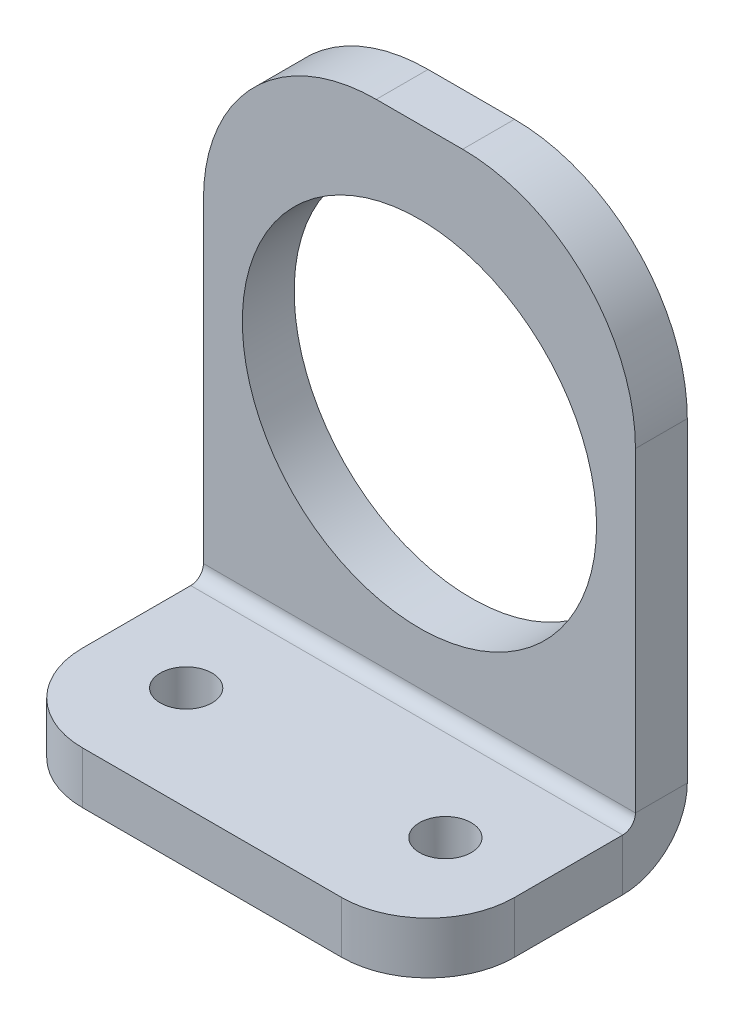
SolidWorks part; units mm, degrees
note: The reader was unsure of these and kept them because the rebuilt part matched: thickness of "基体-法兰1", "边线-法兰1", "钣金1", "钣金2", "钣金3", "钣金4"; flange length of "边线-法兰1".
ref_plane "前视基准面" through (0, 0, 0) normal (0, 0, 1) x (1, 0, 0)
ref_plane "上视基准面" through (0, 0, 0) normal (0, 1, 0) x (1, 0, 0)
ref_plane "右视基准面" through (0, 0, 0) normal (1, 0, 0) x (0, 0, -1)
sketch "草图1" plane through (0, 0, 0) normal (0, 0, 1) x (1, 0, 0)
  line L1 (12.5, -16) -> (-12.5, -16)
  line L2 (12.5, -16) -> (12.5, 16)
  line L3 (12.5, 16) -> (-12.5, 16)
  line L4 (-12.5, -16) -> (-12.5, 16)
  line L5 (12.5, -16) -> (-12.5, 16) construction
  line L6 (12.5, 16) -> (-12.5, -16) construction
  point P0 (0, 0)
  dimension "D1" = 25
  dimension "D2" = 32
base flange "基体-法兰1" sketch "草图1" thickness 3 reverse thickness direction no parameters "D1"=0.7366
edge flange "边线-法兰1" sketch "草图12" flange angle 90 flange length 15 flange position material inside bend radius 0.7366 thickness 3 relief rectangular parameters "D6"=10
sketch "草图12" plane through (0, -16, 0) normal (0, -1, 0) x (1, 0, 0)
  line L0 (-12.5, 0) -> (12.5, 0) construction
  line L1 (-12.5, 0) -> (12.5, 0)
  line L2 (-12.5, 0) -> (-12.5, 12)
  line L3 (-12.5, 12) -> (12.5, 12)
  line L4 (12.5, 12) -> (12.5, 0)
bend "边线折弯1" bend radius 0.7366 bend angle 90 parameters "D5"=1
sketch "草图13" plane through (0, 0, 0) normal (0, 0, 1) x (1, 0, 0)
  line L0 (12.5, -16) -> (-12.5, -16) construction
  line L3 (-12.5, 16) -> (-12.5, -12.2634) construction
  circle A0 centre (0, 1) radius 10.25
  dimension "D1" = 20.5
  dimension "D2" = 17
  dimension "D3" = 12.5
extrude "切除-拉伸1" cut sketch "草图13" against normal blind 10 normal cut yes
sketch "草图15" plane through (0, -13, 0) normal (0, 1, 0) x (1, 0, 0)
  line L0 (0, -0.7366) -> (0, -12) construction
  line L3 (-12.5, -0.7366) -> (12.5, -0.7366) construction
  line L5 (12.5, -12) -> (-12.5, -12) construction
  circle A0 centre (-7.5, -6) radius 1.5
  circle A1 centre (7.5, -6) radius 1.5
  dimension "D1" = 3
  dimension "D2" = 15
  dimension "D3" = 6
extrude "切除-拉伸2" cut sketch "草图15" against normal blind 10 normal cut yes
fillet "圆角1" radius 10 2 edges at (12.5, 16, -1.5) (-12.5, 16, -1.5)
fillet "圆角2" radius 5 2 edges at (12.5, -14.5, 12) (-12.5, -14.5, 12)
sketch "折弯-线1" [suppressed] plane through (0, 0, 0) normal (0, 1, 0) x (1, 0, 0)
sketch "边界框1" [suppressed] plane through (0, 0, 0) normal (0, 1, 0) x (1, 0, 0)
sheet metal parameters "钣金1" thickness 3 parameters "D1"=0.7366
flat pattern "平板型式1" [suppressed]
sketch "折弯-线2" plane through (0, 0, 0) normal (0, 1, 0) x (1, 0, 0)
sketch3d "边界框2" [suppressed]
  line L0 (15, -15, 0) -> (-15, -15, 0) construction
  line L1 (15, 15, 0) -> (-15, 15, 0) construction
  line L2 (15, -15, 0) -> (15, 15, 0) construction
  line L3 (-15, -15, 0) -> (-15, 15, 0) construction
sheet metal parameters "钣金2" thickness 3 parameters "D1"=0.7366, "D7"=2
flat pattern "平板型式1"
sketch "折弯-线2" plane through (0, 0, 0) normal (0, 0, 1) x (1, 0, 0)
  line L0 (-15, -13.6273) -> (15, -13.6273) construction
  line L1 (-15, -13.6273) -> (15, -13.6273) construction
sketch3d "边界框2" [suppressed]
  line L0 (15, 15, 0) -> (15, -27.2546, 0) construction
  line L1 (-15, 15, 0) -> (-15, -27.2546, 0) construction
  line L2 (15, 15, 0) -> (-15, 15, 0) construction
  line L3 (15, -27.2546, 0) -> (-15, -27.2546, 0) construction
bend of the flat pattern "展平-<边线折弯1>1"
sheet metal parameters "钣金3" thickness 3 parameters "D1"=0.7366, "D7"=2
flat pattern "平板型式1"
sketch "折弯-线2" plane through (0, 0, 0) normal (0, 0, 1) x (1, 0, 0)
  line L0 (-15, -13.6273) -> (15, -13.6273) construction
  line L1 (-15, -13.6273) -> (15, -13.6273) construction
sketch3d "边界框2" [suppressed]
  line L0 (15, 15, 0) -> (15, -27.2546, 0) construction
  line L1 (-15, 15, 0) -> (-15, -27.2546, 0) construction
  line L2 (15, 15, 0) -> (-15, 15, 0) construction
  line L3 (15, -27.2546, 0) -> (-15, -27.2546, 0) construction
bend of the flat pattern "展平-<边线折弯1>1"
sheet metal parameters "钣金4" thickness 3 parameters "D1"=0.7366, "D7"=2
flat pattern "平板型式1"
sketch "折弯-线2" plane through (0, 0, 0) normal (0, 0, 1) x (1, 0, 0)
  line L0 (-12.5, -14.02) -> (12.5, -14.02) construction
  line L1 (-12.5, -14.02) -> (12.5, -14.02) construction
sketch3d "边界框2" [suppressed]
  line L0 (12.5, 16, 0) -> (12.5, -27.04, 0) construction
  line L1 (-12.5, 16, 0) -> (-12.5, -27.04, 0) construction
  line L2 (12.5, 16, 0) -> (-12.5, 16, 0) construction
  line L3 (12.5, -27.04, 0) -> (-12.5, -27.04, 0) construction
bend of the flat pattern "展平-<边线折弯1>1"
